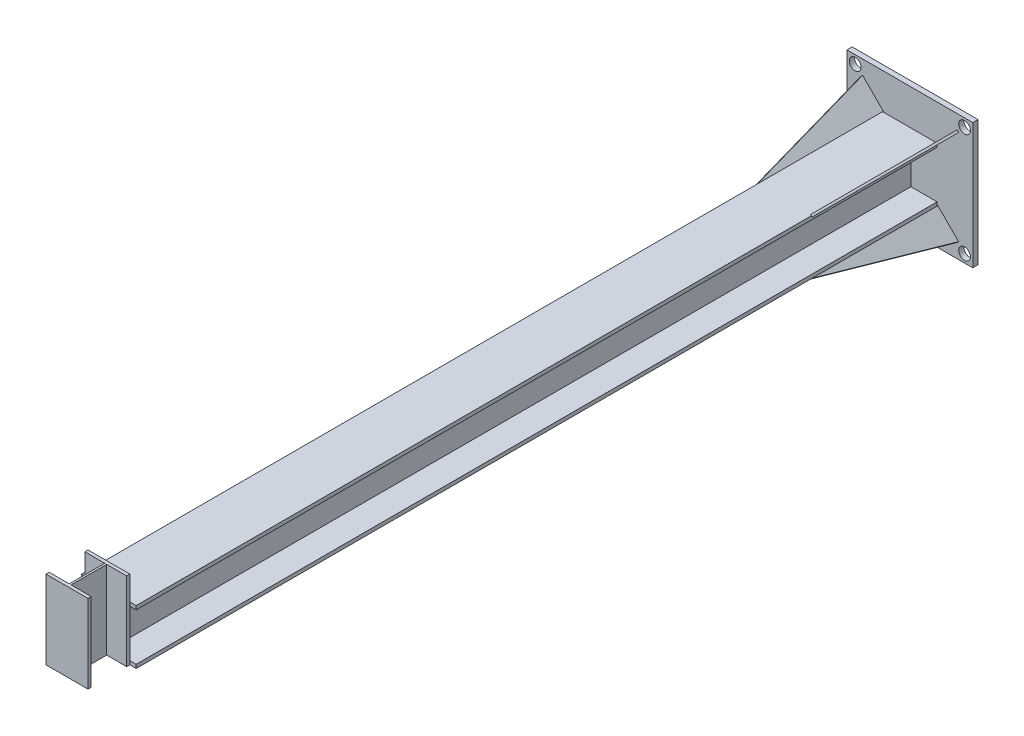
SolidWorks part; units mm, degrees
ref_plane "Front Plane" through (0, 0, 0) normal (0, 0, 1) x (1, 0, 0)
ref_plane "Top Plane" through (0, 0, 0) normal (0, 1, 0) x (1, 0, 0)
ref_plane "Right Plane" through (0, 0, 0) normal (1, 0, 0) x (0, 0, -1)
sketch "Sketch1" plane through (0, 0, 0) normal (0, 0, 1) x (1, 0, 0)
  line L0 (-125, 242.5) -> (0, 242.5)
  line L1 (-135, 17.5) -> (-260, 17.5)
  line L24 (-260, 260) -> (0, 260)
  line L25 (0, 0) -> (-260, 0)
  line L26 (-260, 260) -> (-260, 242.5)
  line L27 (-260, 242.5) -> (-135, 242.5)
  line L28 (0, 260) -> (0, 242.5)
  line L30 (-260, 0) -> (-260, 17.5)
  line L31 (0, 17.5) -> (-125, 17.5)
  line L32 (0, 0) -> (0, 17.5)
  line L34 (-135, 17.5) -> (-135, 242.5)
  line L35 (-125, 17.5) -> (-125, 242.5)
extrude "Boss-Extrude1" add sketch "Sketch1" along normal blind 3820
sketch "Sketch3" plane through (0, 0, 0) normal (0, 0, 1) x (1, 0, 0)
  line L1 (170, -170) -> (-430, -170)
  line L2 (170, -170) -> (170, 430)
  line L3 (170, 430) -> (-430, 430)
  line L4 (-430, -170) -> (-430, 430)
  line L6 (0, 260) -> (-260, 260) construction
  line L7 (-125, 17.5) -> (-125, 242.5) construction
  point P13 (-130, 260)
  point P14 (-125, 130)
  dimension "D1" = 600
  dimension "D2" = 600
  dimension "D3" = 300
  dimension "D4" = 300
extrude "Boss-Extrude2" add sketch "Sketch3" against normal blind 25 separate body
sketch "Sketch4" plane through (0, 0, 0) normal (0, 0, 1) x (1, 0, 0)
  line L0 (170, 430) -> (-430, 430) construction
  line L1 (-430, 430) -> (-430, -170) construction
  line L2 (170, -170) -> (170, 430) construction
  line L3 (-430, -170) -> (170, -170) construction
  circle A0 centre (-391, 391) radius 28
  circle A1 centre (131, 391) radius 28
  circle A2 centre (131, -131) radius 28
  circle A3 centre (-391, -131) radius 28
  dimension "D1" = 39
  dimension "D2" = 39
  dimension "D3" = 39
  dimension "D4" = 39
  dimension "D5" = 39
  dimension "D6" = 39
  dimension "D7" = 39
  dimension "D8" = 39
ref_plane "Plane1" through (0, 0, 0) normal (-0.7071, -0.7071, 0) x (0.7071, -0.7071, 0)
sketch "Sketch5" plane through (0, 0, 0) normal (-0.7071, -0.7071, 0) x (0.7071, -0.7071, 0)
  line L0 (0, 0) -> (140, 0)
  line L1 (0, 0) -> (0, 600)
  line L2 (0, 3820) -> (0, 0) construction
  line L3 (0, 600) -> (140, 0)
extrude "Boss-Extrude5" add sketch "Sketch5" along normal mid plane 10 separate body
ref_point "Point1"
ref_axis "Axis1" through (-130, 130, 3820) along (0, 0, -1)
pattern_circular "CirPattern3" count 4 over 360 about axis through (-130, 130, 3820) along (0, 0, -1) of bodies 106
sketch "Sketch6" plane through (0, 0, 0) normal (0, -1, 0) x (1, 0, 0)
  line L0 (-230, 4020) -> (-30, 4020)
  line L1 (-230, 4020) -> (-230, 4005)
  line L2 (-230, 3820) -> (-230, 3835)
  line L3 (-30, 3820) -> (-30, 3835)
  line L4 (-30, 3820) -> (-230, 3820)
  line L5 (-30, 4020) -> (-30, 4005)
  line L6 (-230, 4005) -> (-134.5, 4005)
  line L7 (-125.5, 4005) -> (-30, 4005)
  line L8 (-30, 3835) -> (-125.5, 3835)
  line L9 (-134.5, 3835) -> (-134.5, 4005)
  line L10 (-125.5, 3835) -> (-125.5, 4005)
  line L11 (-134.5, 3835) -> (-230, 3835)
  line L12 (-260, 3820) -> (0, 3820) construction
  line L14 (0, 3820) -> (-260, 3820) construction
extrude "Boss-Extrude6" add sketch "Sketch6" against normal blind 375 separate body
sketch "Sketch7" plane through (0, 0, 0) normal (0, 0, 1) x (1, 0, 0)
  line L0 (170, -170) -> (170, 430) construction
  line L1 (170, 430) -> (-430, 430) construction
  circle A0 centre (-391, 391) radius 28
  circle A1 centre (131, 391) radius 28
  circle A2 centre (131, -131) radius 28
  circle A3 centre (-391, -131) radius 28
  point P9 (0, 0)
  dimension "D1" = 522
  dimension "D2" = 522
  dimension "D3" = 522
  dimension "D4" = 522
  dimension "D5" = 39
  dimension "D6" = 39
extrude "Cut-Extrude2" cut sketch "Sketch7" against normal through all
